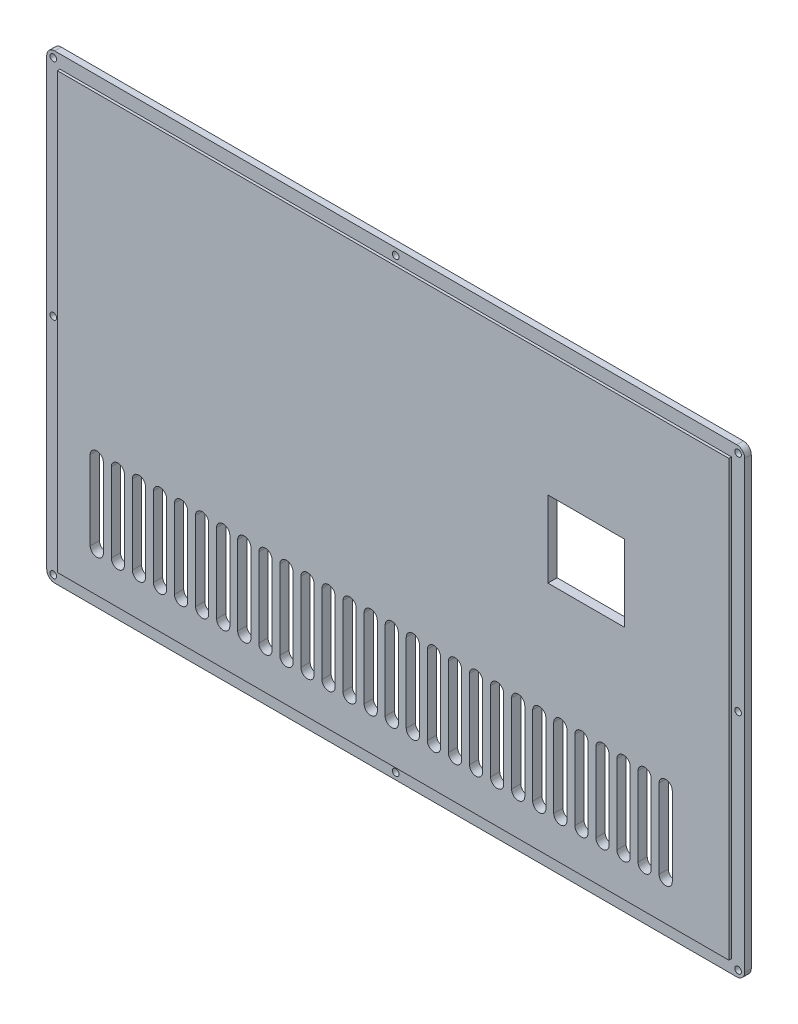
SolidWorks part; units mm, degrees
ref_plane "Front Plane" through (0, 0, 0) normal (0, 0, 1) x (1, 0, 0)
ref_plane "Top Plane" through (0, 0, 0) normal (0, 1, 0) x (1, 0, 0)
ref_plane "Right Plane" through (0, 0, 0) normal (1, 0, 0) x (0, 0, -1)
sketch "Sketch1" plane through (0, 0, 0) normal (0, 0, 1) x (1, 0, 0)
  line L1 (-132.5, 87.5) -> (132.5, 87.5)
  line L2 (-132.5, 87.5) -> (-132.5, -87.5)
  line L3 (-132.5, -87.5) -> (132.5, -87.5)
  line L4 (132.5, 87.5) -> (132.5, -87.5)
  point P4 (-132.5, 0)
  point P6 (0, 87.5)
  dimension "D1" = 265
  dimension "D2" = 175
extrude "Boss-Extrude1" add sketch "Sketch1" along normal blind 2.5
sketch "Sketch2" plane through (0, 0, 2.5) normal (0, 0, 1) x (1, 0, 0)
  line L0 (132.5, 87.5) -> (-132.5, 87.5) construction
  line L1 (-127.5, 82.5) -> (127.5, 82.5)
  line L2 (-127.5, 82.5) -> (-127.5, -82.5)
  line L3 (-127.5, -82.5) -> (127.5, -82.5)
  line L4 (127.5, 82.5) -> (127.5, -82.5)
  line L5 (-132.5, 87.5) -> (-132.5, -87.5) construction
  point P4 (-127.5, 0)
  point P6 (0, 82.5)
  dimension "D1" = 5
  dimension "D2" = 5
extrude "Boss-Extrude2" add sketch "Sketch2" along normal blind 1
sketch "Sketch3" plane through (0, 0, 0) normal (0, 0, -1) x (-1, 0, 0)
  line L0 (132.5, -87.5) -> (-132.5, -87.5) construction
  line L1 (132.5, 87.5) -> (132.5, -87.5) construction
  line L2 (110, -67.5) -> (110, -37.5)
  line L3 (115, -67.5) -> (115, -37.5)
  arc A0 (110, -67.5) -> (115, -67.5) centre (112.5, -67.5) ccw
  arc A1 (115, -37.5) -> (110, -37.5) centre (112.5, -37.5) ccw
  point P11 (112.5, -35)
  point P15 (112.5, -70)
  dimension "D1" = 5
  dimension "D2" = 20
  dimension "D3" = 20
  dimension "D4" = 30
extrude "Cut-Extrude1" cut sketch "Sketch3" against normal through all
pattern_linear "LPattern1" count 28 spacing 8 along (1, 0, 0) of "Cut-Extrude1"
mirror "Mirror2" [suppressed] about plane through (0, 0, 0) normal (0, 1, 0)
fillet "Fillet3" radius 3 4 edges at (132.5, -87.5, 1.25) (132.5, 87.5, 1.25) (-132.5, 87.5, 1.25) (-132.5, -87.5, 1.25)
sketch "Sketch5" plane through (0, 0, 0) normal (0, 0, -1) x (-1, 0, 0)
  line L1 (-58.78, 7.14) -> (-87.78, 7.14)
  line L2 (-58.78, 7.14) -> (-58.78, 36.14)
  line L3 (-58.78, 36.14) -> (-87.78, 36.14)
  line L4 (-87.78, 7.14) -> (-87.78, 36.14)
  line L5 (-132.5, -84.5) -> (-132.5, 84.5) construction
  point P4 (-58.78, 21.64)
  point P5 (-73.28, 7.14)
  dimension "D1" = 29
  dimension "D2" = 29
  dimension "D3" = 21.64
  dimension "D4" = 59.22
extrude "Cut-Extrude3" cut sketch "Sketch5" against normal through all
sketch "Sketch6" plane through (0, 0, 0) normal (0, 0, -1) x (-1, 0, 0)
  line L0 (82.3683, 69.1692) -> (64.677, 58.9055)
  line L1 (64.677, 58.9055) -> (82.3683, 48.7903)
  line L2 (82.3683, 48.7903) -> (82.3683, 69.1692)
  line L3 (56.8332, 58.9055) -> (86.1621, 75.9208)
  line L4 (86.1621, 75.9208) -> (86.1621, 42.1365)
  line L5 (86.1621, 42.1365) -> (56.8332, 58.9055)
  line L6 (56.7266, 18.825) -> (86.1086, 35.7485)
  line L7 (86.1086, 35.7485) -> (86.1086, 1.9641)
  line L8 (86.1086, 1.9641) -> (56.7266, 18.825)
  line L9 (91.5845, 38.9118) -> (120.9135, 55.9273)
  line L10 (120.9135, 55.9273) -> (120.9135, 22.1429)
  line L11 (120.9135, 22.1429) -> (91.5845, 38.9118)
  line L12 (89.75, 35.7345) -> (119.0791, 18.9656)
  line L13 (119.0791, 18.9656) -> (89.75, 1.9502)
  line L14 (89.75, 1.9502) -> (89.75, 35.7345)
  line L15 (55.2024, 55.7714) -> (84.6379, 38.9413)
  line L16 (84.6379, 38.9413) -> (55.2024, 21.987)
  line L17 (55.2024, 21.987) -> (55.2024, 55.7714)
  line L18 (89.7597, 75.3359) -> (119.0888, 58.5054)
  line L19 (119.0888, 58.5054) -> (89.7597, 41.4898)
  line L20 (89.7597, 41.4898) -> (89.7597, 75.3359)
extrude "Boss-Extrude3" add sketch "Sketch6" along normal blind 0.5
sketch "Sketch7" plane through (0, 0, 0) normal (0, 0, -1) x (-1, 0, 0)
  line L0 (-129.5, 87.5) -> (129.5, 87.5) construction
  line L1 (130, 85) -> (-130, 85) construction
  line L2 (130, 85) -> (130, -85) construction
  line L3 (130, -85) -> (-130, -85) construction
  line L4 (-130, 85) -> (-130, -85) construction
  line L5 (129.5, -87.5) -> (-129.5, -87.5) construction
  line L6 (132.5, 84.5) -> (132.5, -84.5) construction
  line L7 (-132.5, -84.5) -> (-132.5, 84.5) construction
  circle A0 centre (130, -85) radius 1.25
  circle A1 centre (130, 0) radius 1.25
  circle A2 centre (130, 85) radius 1.25
  circle A3 centre (0, 85) radius 1.25
  circle A4 centre (-130, 85) radius 1.25
  circle A5 centre (-130, 0) radius 1.25
  circle A6 centre (-130, -85) radius 1.25
  circle A7 centre (0, -85) radius 1.25
  point P13 (125, 82.5)
  point P14 (0, 0)
  point P15 (0, 0)
  point P16 (0, 0)
  point P17 (125, -82.5)
  point P18 (0, 0)
  point P19 (125, -82.7509)
  point P20 (125, -82.5)
  point P23 (125, 0)
  point P24 (0, 0)
  point P25 (125, 0)
  point P26 (0, 0)
  point P27 (0, 0)
  point P29 (124.557, 81.5446)
  point P32 (0, 0)
  point P33 (0, 82.5)
  point P34 (0, 0)
  point P36 (-87.3815, 80.8577)
  point P39 (-125, 0)
  point P40 (-125, -82.5)
  point P42 (-124.4516, -78.7739)
  point P45 (0, -82.5)
  dimension "D5" = 2.5
  dimension "D1" = 2.5
  dimension "D2" = 2.5
  dimension "D3" = 2.5
  dimension "D4" = 2.5
extrude "Cut-Extrude4" cut sketch "Sketch7" against normal through all
